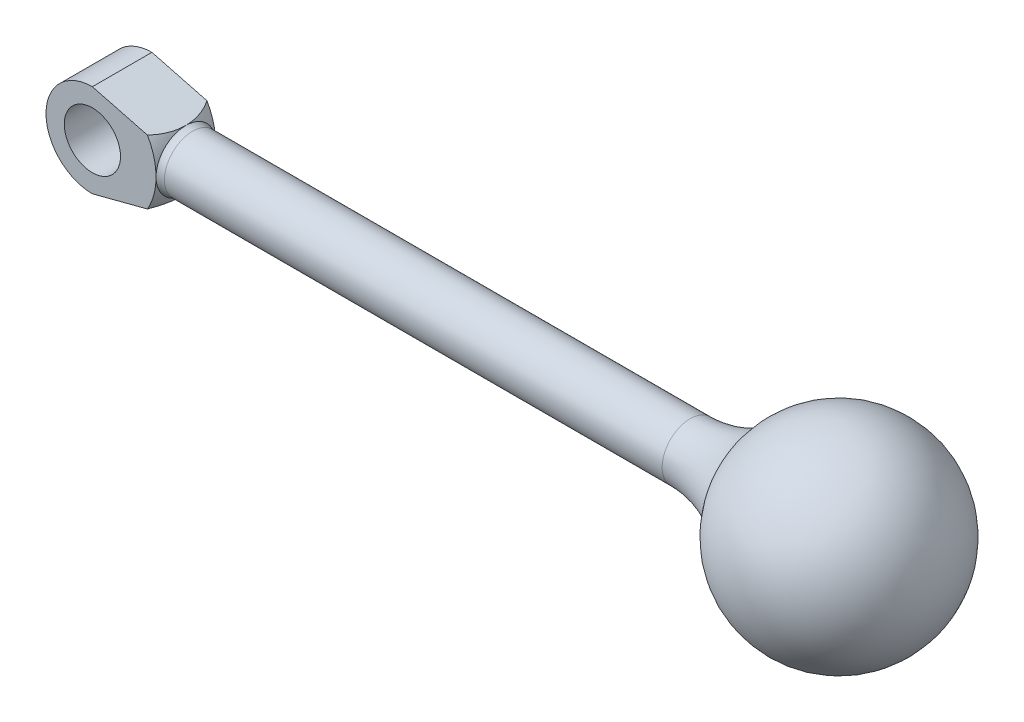
SolidWorks part; units mm, degrees
ref_plane "Alzado" through (0, 0, 0) normal (0, 0, 1) x (1, 0, 0)
ref_plane "Planta" through (0, 0, 0) normal (0, 1, 0) x (1, 0, 0)
ref_plane "Vista lateral" through (0, 0, 0) normal (1, 0, 0) x (0, 0, -1)
sketch "Croquis1" plane through (0, 0, 0) normal (0, 1, 0) x (1, 0, 0)
  line L0 (0, 0) -> (-21.1795, 0) construction
  line L1 (0, 0) -> (-14, 0)
  arc A0 (-14, 0) -> (0, 0) centre (-7, 0) ccw
  dimension "D1" = 14
revolve "Revolución1" add sketch "Croquis1" angle 360 about L0
sketch "Croquis2" plane through (0, 0, 0) normal (0, 1, 0) x (1, 0, 0)
  line L0 (0, 0) -> (-52.1475, 0) construction
  line L1 (-14, 0) -> (-63, 0)
  line L2 (-52.9931, -2) -> (-17.5844, -2)
  line L3 (-14, 0) -> (-13.1323, -3.3757)
  circle A0 centre (-7, 0) radius 7 construction
  arc A1 (-63, 0) -> (-53.4706, -2.1176) centre (-58, 0) ccw
  arc A2 (-53.4706, -2.1176) -> (-52.9931, -2) centre (-53, -3) cw
  arc A3 (-17.5844, -2) -> (-13.1323, -3.3757) centre (-17.5844, -9.8918) cw
  dimension "D3" = 5
  dimension "D4" = 1
  dimension "D1" = 49
  dimension "D2" = 2
  dimension "D5" = 53
revolve "Revolución2" add sketch "Croquis2" angle 360 about L0
sketch "Croquis3" plane through (0, 0, 0) normal (0, 1, 0) x (1, 0, 0)
  line L1 (-53.4706, 2.1176) -> (-64.1158, 2.1176)
  line L3 (-53.4706, -2.1176) -> (-64.1158, -2.1176)
  line L5 (-64.1158, 2.1176) -> (-53.4706, 2.1176)
  line L6 (-64.1158, 2.1176) -> (-64.1158, 5.5171)
  line L7 (-64.1158, 5.5171) -> (-53.4706, 5.5171)
  line L8 (-53.4706, 2.1176) -> (-53.4706, 5.5171)
  line L9 (-53.4706, -2.1176) -> (-64.1158, -2.1176)
  line L10 (-53.4706, -2.1176) -> (-53.4706, -5.3342)
  line L11 (-53.4706, -5.3342) -> (-64.1158, -5.3342)
  line L12 (-64.1158, -2.1176) -> (-64.1158, -5.3342)
extrude "Cortar-Extruir1" cut sketch "Croquis3" against normal blind 10 and the other way blind 10 contours L1 L8 L7 L6 | L3 L12 L11 L10 region at (-58.7932, 0, -3.8174) region at (-58.7932, 0, 3.7259)
sketch "Croquis4" plane through (0, 0, -2.1176) normal (0, 0, -1) x (-1, 0, 0)
  circle A0 centre (58, 0) radius 2
  dimension "D1" = 4
extrude "Cortar-Extruir2" cut sketch "Croquis4" against normal blind 10
sketch "Croquis5" plane through (0, 0, 2.1176) normal (0, 0, 1) x (1, 0, 0)
  line L0 (-58, -3.2995) -> (-53.4706, -2.1176)
  line L1 (-58, 3.2995) -> (-53.4706, 2.1176)
  arc A0 (-58, 3.2995) -> (-58, -3.2995) centre (-58, 0) ccw
  arc A1 (-53.4706, 2.1176) -> (-53.4706, -2.1176) centre (-58, 0) ccw
  arc A2 (-52.9931, -2) -> (-53.4706, -2.1176) centre (-53, -3) ccw construction
extrude "Cortar-Extruir3" cut sketch "Croquis5" against normal blind 12
